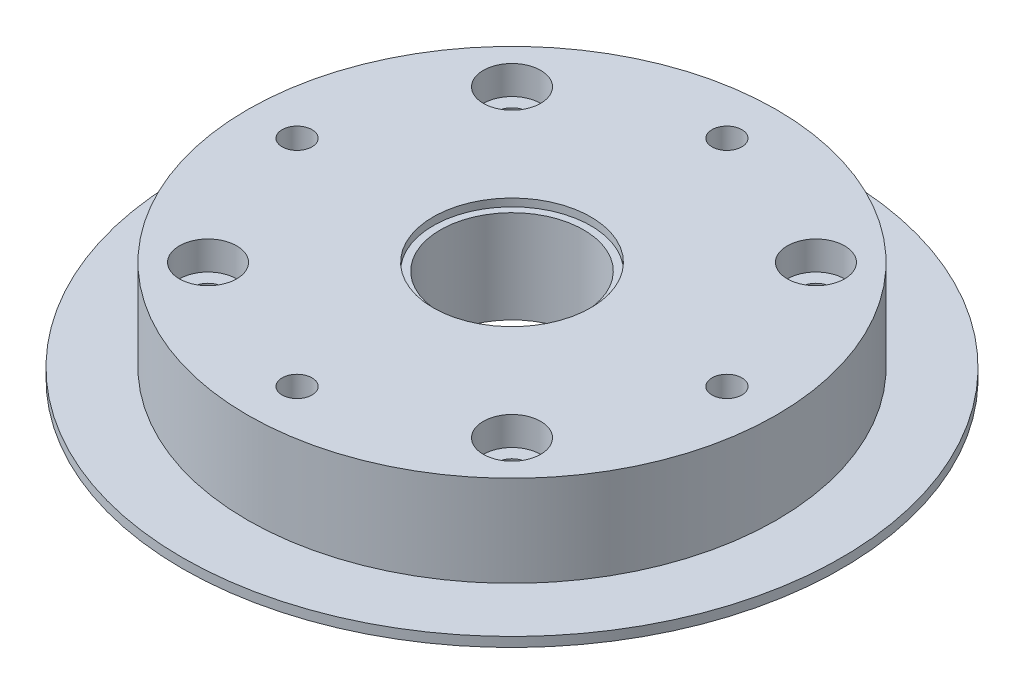
SolidWorks part; units mm, degrees
ref_plane "Front Plane" through (0, 0, 0) normal (0, 0, 1) x (1, 0, 0)
ref_plane "Top Plane" through (0, 0, 0) normal (0, 1, 0) x (1, 0, 0)
ref_plane "Right Plane" through (0, 0, 0) normal (1, 0, 0) x (0, 0, -1)
sketch "Sketch1" plane through (0, 0, 0) normal (0, 1, 0) x (1, 0, 0)
  line L0 (0, 0) -> (22.5, 0) construction
  circle A0 centre (0, 0) radius 34.5
  circle A1 centre (22.5, 0) radius 1.5635
  circle A2 centre (15.9099, -15.9099) radius 1.5635
  circle A3 centre (0, -22.5) radius 1.5635
  circle A4 centre (-15.9099, -15.9099) radius 1.5635
  circle A5 centre (-22.5, 0) radius 1.5635
  circle A6 centre (-15.9099, 15.9099) radius 1.5635
  circle A7 centre (0, 22.5) radius 1.5635
  circle A8 centre (15.9099, 15.9099) radius 1.5635
  circle A9 centre (0, 0) radius 8.25
  circle A10 centre (0, 0) radius 27.69
  circle A11 centre (0, 0) radius 7.5
  point P14 (0, 0)
  dimension "D2" = 69
  dimension "D3" = 16.5
  dimension "D5" = 3.127
  dimension "D6" = 55.38
  dimension "D7" = 15
  dimension "D4" = 22.5
  dimension "D1" = 8
extrude "Boss-Extrude1" add sketch "Sketch1" against normal blind 1 contours A0 A10 | A10 A2 A3 A4 A5 A6 A7 A8 A9 A1 | A11 A9 region at (-33.5242, 0, 0) region at (-8.0167, 0, 0) region at (-26.9068, 0, 0)
extrude "Boss-Extrude2" add sketch "Sketch1<3>" along normal blind 9.525 contours A10 A2 A3 A4 A5 A6 A7 A8 A9 A1 | A11 A9 region at (-8.0167, 0, 0) region at (-26.9068, 0, 0)
sketch "Sketch1<3>" plane through (0, 0, 0) normal (0, 1, 0) x (1, 0, 0) same geometry as "Sketch1"
sketch "Sketch2" plane through (0, 9.525, 0) normal (0, 1, 0) x (1, 0, 0)
  circle A0 centre (15.9099, 15.9099) radius 3
  circle A1 centre (15.9099, -15.9099) radius 3
  circle A2 centre (-15.9099, -15.9099) radius 3
  circle A3 centre (-15.9099, 15.9099) radius 3
  point P12 (0, 0)
  circle M4 centre (-15.9099, -15.9099) radius 1.5635
  circle M6 centre (-15.9099, 15.9099) radius 1.5635
  circle M8 centre (15.9099, 15.9099) radius 1.5635
  dimension "D1" = 6
  dimension "D2" = 4
extrude "Cut-Extrude1" cut sketch "Sketch2" against normal blind 3 contours A3 M6 | A0 M8 | A2 M4 | A1 region at (12.9948, 9.525, -15.9099) region at (-18.825, 9.525, 15.9099) region at (-18.825, 9.525, -15.9099)
sketch "Sketch3" plane through (0, -1, 0) normal (0, -1, 0) x (1, 0, 0)
  circle A0 centre (22.5, 0) radius 1.925
  circle A1 centre (0, -22.5) radius 1.925
  circle A2 centre (-22.5, 0) radius 1.925
  circle A3 centre (0, 22.5) radius 1.925
  point P12 (0, 0)
  dimension "D1" = 3.85
  dimension "D2" = 4
extrude "Cut-Extrude2" cut sketch "Sketch3" against normal blind 4
extrude "Cut-Extrude3" cut sketch "Sketch1<6>" against normal blind 0.8 from offset 9.525 contours A11 A9 region at (-8.0167, 0, 0)
sketch "Sketch1<6>" plane through (0, 0, 0) normal (0, 1, 0) x (1, 0, 0) same geometry as "Sketch1"
equation "\"D1@Boss-Extrude2\"=\"sheetThickness\"*2"
equation "\"largeBearOD\"= 21mm"
equation "\"largeBearID\"= 15mm"
equation "\"largeBearOTight\"= 0.127mm'calibrate - hold onto gears"
equation "\"largeBearITight\"= 0mm'calibrate - hold onto eccentric nut"
equation "\"largeBearFlangeDiam\"= 22.5mm"
equation "\"largeBearFlangeWidth\"= 0.8mm"
equation "\"smallBearOD\"= 15mm"
equation "\"smallBearOTight\"= 0mm'calibrate - hold onto bottom of gearbox"
equation "\"smallBearOLoose\"= 0mm'calibrate - able to take off topHat"
equation "\"smallBearID\"= 10mm"
equation "\"smallBearITight\"= 0mm'hold onto "
equation "\"pinCircleDiam\"= 75mm"
equation "\"pinDiam\"= 6mm"
equation "\"sheetThickness\"= 0.1875in"
equation "\"ballBearDiam\"= 3.214mm"
equation "\"thrustBearingThickness\"= 5mm'measure this irl and change"
equation "\"thrustBearingID\"= 0mm'measure this irl and change"
equation "\"thrustBearingOD\"= 0mm'measure this irl and change"
equation "\"eccentricity\"= 1mm"
equation "\"D7@Sketch1\"=\"smallBearOD\"+\"smallBearOTight\""
equation "\"D19@Cut-Extrude3\"=\"sheetThickness\"*2"
equation "\"D2@Sketch1\"=\"pinCircleDiam\"-\"pinDiam\""
